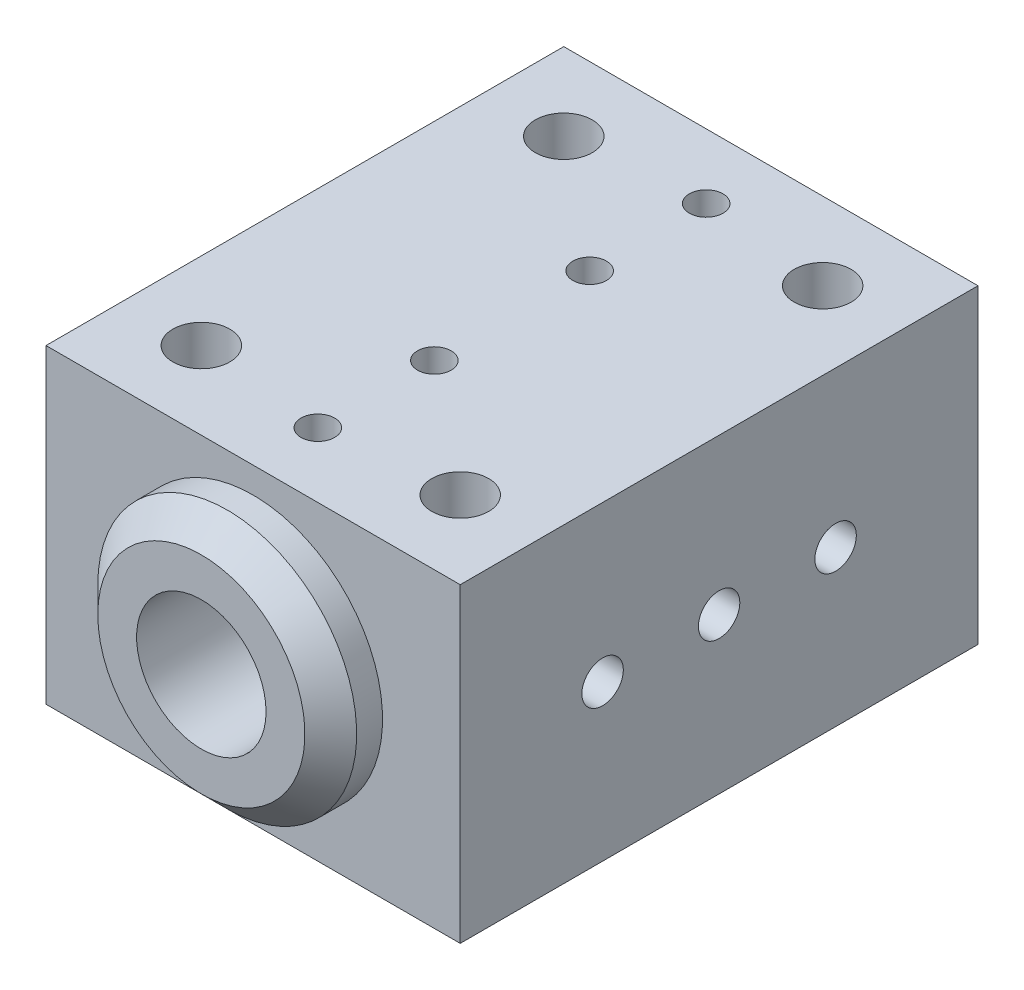
SolidWorks part; units mm, degrees
ref_plane "Front Plane" through (0, 0, 0) normal (0, 0, 1) x (1, 0, 0)
ref_plane "Top Plane" through (0, 0, 0) normal (0, 1, 0) x (1, 0, 0)
ref_plane "Right Plane" through (0, 0, 0) normal (1, 0, 0) x (0, 0, -1)
sketch "Base Sketch" plane through (0, 0, 0) normal (0, 1, 0) x (1, 0, 0)
  line L1 (-8, -10) -> (8, -10)
  line L2 (-8, -10) -> (-8, 10)
  line L3 (-8, 10) -> (8, 10)
  line L4 (8, -10) -> (8, 10)
  line L5 (-8, -10) -> (8, 10) construction
  line L6 (-8, 10) -> (8, -10) construction
  point P0 (0, 0)
  dimension "D1" = 20
  dimension "D2" = 16
extrude "Base Extrude" add sketch "Base Sketch" along normal blind 12
sketch "Protrusion Sketch" plane through (0, 0, 0) normal (0, 0, 1) x (1, 0, 0)
  line L0 (-8, 12) -> (-8, 0) construction
  circle A0 centre (0, 6) radius 5
  point P5 (-8, 6)
  dimension "D1" = 10
extrude "Top Protrusion Extrude" add sketch "Protrusion Sketch" along normal blind 2 from surface starting at face at (0, 6, 10)
extrude "Bottom Protrusion Extrude" add sketch "Protrusion Sketch<2>" against normal blind 2 from surface starting at face at (0, 6, -10)
sketch "Protrusion Sketch<2>" plane through (0, 0, 0) normal (0, 0, 1) x (1, 0, 0) same geometry as "Protrusion Sketch"
chamfer "Protrusion Chamfer" distance 1 2 edges at (5, 6, -12) (-5, 6, 12)
hole_wizard "Ø5.0mm Dowel Hole1" positions "Sketch3" profile "Sketch4" hole size "Ø5.0" standard "ANSI Metric" end condition through all
sketch "Sketch3" plane through (0, 0, 12) normal (0, 0, 1) x (1, 0, 0)
  point P0 (0, 6)
sketch "Sketch4" plane through (0, 6, 12) normal (1, 0, 0) x (0, -1, 0)
  line L0 (0, 0) -> (0, 24)
  line L1 (0, 24) -> (2.5, 24)
  line L2 (2.5, 24) -> (2.5, 0)
  line L5 (2.5, 0) -> (0, 0)
  line L11 (0, -6.35) -> (0, 107.95) construction
  dimension "Thru Hole Dia." = 5
  dimension "Thru Hole Depth" = 24
sketch "Right Hole Locations" plane through (0, 0, 0) normal (1, 0, 0) x (0, 0, -1)
  line L1 (-10, 12) -> (-10, 0) construction
  point P0 (0, 6)
  point P1 (4.5, 6)
  point P4 (-4.5, 6)
  point P5 (-10, 6)
  dimension "D1" = 4.5
  dimension "D2" = 4.5
hole_wizard "Ø1.6mm Dowel Hole1" positions "Sketch20" profile "Sketch21" hole size "Ø2.0" standard "ANSI Metric"
sketch "Sketch20" plane through (8, 0, 0) normal (1, 0, 0) x (0, 0, -1)
  point P0 (0, 6)
sketch "Sketch21" plane through (8, 6, 0) normal (0, 1, 0) x (0, 0, -1)
  line L0 (0, 0) -> (0, 8.4807)
  line L1 (0, 8.4807) -> (0.8, 8)
  line L2 (0.8, 8) -> (0.8, 0)
  line L5 (0.8, 0) -> (0, 0)
  line L10 (0, 8.4807) -> (-0.8, 8) construction
  line L11 (0, -6.35) -> (0, 107.95) construction
  dimension "Hole Dia." = 1.6
  dimension "Hole Depth" = 8
  dimension "Drill Angle" = 118
hole_wizard "Ø1.6 (1.6) Diameter Hole4" positions "Sketch39" profile "Sketch40" hole size "Ø1.6" standard "ANSI Metric"
sketch "Sketch39" plane through (-8, 0, 0) normal (-1, 0, 0) x (0, 0, 1)
  point P0 (0, 6)
sketch "Sketch40" plane through (-8, 6, 0) normal (0, 1, 0) x (0, 0, 1)
  line L0 (0, 0) -> (0, 3.9807)
  line L1 (0, 3.9807) -> (0.8, 3.5)
  line L2 (0.8, 3.5) -> (0.8, 0)
  line L5 (0.8, 0) -> (0, 0)
  line L10 (0, 3.9807) -> (-0.8, 3.5) construction
  line L11 (0, -6.35) -> (0, 107.95) construction
  dimension "Hole Dia." = 1.6
  dimension "Hole Depth" = 3.5
  dimension "Drill Angle" = 118
hole_wizard "M2x0.4 Tapped Hole1" positions "Sketch41" profile "Sketch42" tap size "M2x0.4" standard "ANSI Metric"
sketch "Sketch41" plane through (8, 0, 0) normal (1, 0, 0) x (0, 0, -1)
  point P0 (-4.5, 6)
  point P3 (4.5, 6)
sketch "Sketch42" plane through (8, 6, 4.5) normal (0, 1, 0) x (0, 0, -1)
  line L0 (0, 0) -> (0, 4.4807)
  line L1 (0, 4.4807) -> (0.8, 4)
  line L2 (0.8, 4) -> (0.8, 0)
  line L5 (0.8, 0) -> (0, 0)
  line L10 (0, 4.4807) -> (-0.8, 4) construction
  line L11 (0, -6.35) -> (0, 107.95) construction
  dimension "Tap Drill Dia." = 1.6
  dimension "Tap Drill Depth" = 4
  dimension "Drill Angle" = 118
cosmetic thread "Hole Thread1" parameters "D1"=4, "D2"=2
cosmetic thread "Hole Thread2" parameters "D1"=4, "D2"=2
hole_wizard "M2x0.4 Tapped Hole2" positions "Sketch43" profile "Sketch44" tap size "M2x0.4" standard "ANSI Metric"
sketch "Sketch43" plane through (-8, 0, 0) normal (-1, 0, 0) x (0, 0, 1)
  point P0 (-4.5, 6)
  point P3 (4.5, 6)
sketch "Sketch44" plane through (-8, 6, -4.5) normal (0, 1, 0) x (0, 0, 1)
  line L0 (0, 0) -> (0, 4.4807)
  line L1 (0, 4.4807) -> (0.8, 4)
  line L2 (0.8, 4) -> (0.8, 0)
  line L5 (0.8, 0) -> (0, 0)
  line L10 (0, 4.4807) -> (-0.8, 4) construction
  line L11 (0, -6.35) -> (0, 107.95) construction
  dimension "Tap Drill Dia." = 1.6
  dimension "Tap Drill Depth" = 4
  dimension "Drill Angle" = 118
cosmetic thread "Hole Thread3" parameters "D1"=4, "D2"=2
cosmetic thread "Hole Thread4" parameters "D1"=4, "D2"=2
sketch "Top Hole Locations" plane through (0, 0, 0) normal (0, 1, 0) x (1, 0, 0)
  line L0 (-8, 10) -> (-8, -10) construction
  line L1 (-5, -7) -> (5, -7) construction
  line L2 (-5, -7) -> (-5, 7) construction
  line L3 (-5, 7) -> (5, 7) construction
  line L4 (5, -7) -> (5, 7) construction
  line L5 (-5, -7) -> (5, 7) construction
  line L6 (-5, 7) -> (5, -7) construction
  line L7 (8, 10) -> (-8, 10) construction
  point P0 (0, 0)
  dimension "D1" = 3
  dimension "D2" = 3
hole_wizard "Ø2.2 (2.2) Diameter Hole1" positions "Sketch16" profile "Sketch17" hole size "Ø2.2" standard "ANSI Metric" end condition through all
sketch "Sketch16" plane through (0, 12, 0) normal (0, 1, 0) x (1, 0, 0)
  point P0 (-5, 7)
  point P3 (5, 7)
  point P6 (-5, -7)
  point P9 (5, -7)
sketch "Sketch17" plane through (-5, 12, -7) normal (1, 0, 0) x (0, 0, 1)
  line L0 (0, 0) -> (0, 12)
  line L1 (0, 12) -> (1.1, 12)
  line L2 (1.1, 12) -> (1.1, 0)
  line L5 (1.1, 0) -> (0, 0)
  line L11 (0, -6.35) -> (0, 107.95) construction
  dimension "Thru Hole Dia." = 2.2
  dimension "Thru Hole Depth" = 12
sketch "Hole Locations For Slots" plane through (0, 0, 0) normal (0, 1, 0) x (1, 0, 0)
  line L0 (-8, 10) -> (-8, -10) construction
  line L4 (-4, -12) -> (4, -12) construction
  line L5 (4, 12) -> (-4, 12) construction
  point P0 (0, 7.5)
  point P1 (0, 3)
  point P2 (0, -3)
  point P3 (0, -7.5)
  point P9 (-5, 0)
  dimension "D1" = 4.5
  dimension "D2" = 4.5
  dimension "D3" = 4.5
  dimension "D4" = 4.5
  dimension "D5" = 3
hole_wizard "Ø1.3 (1.3) Diameter Hole1" positions "Sketch31" profile "Sketch32" hole size "Ø1.3" standard "ANSI Metric"
sketch "Sketch31" plane through (0, 0, 0) normal (0, -1, 0) x (-1, 0, 0)
  point P0 (0, 7.5)
  point P3 (0, -7.5)
sketch "Sketch32" plane through (0, 0, -7.5) normal (1, 0, 0) x (0, 0, -1)
  line L0 (0, 0) -> (0, 6.3906)
  line L1 (0, 6.3906) -> (0.65, 6)
  line L2 (0.65, 6) -> (0.65, 0)
  line L5 (0.65, 0) -> (0, 0)
  line L10 (0, 6.3906) -> (-0.65, 6) construction
  line L11 (0, -6.35) -> (0, 107.95) construction
  dimension "Hole Dia." = 1.3
  dimension "Hole Depth" = 6
  dimension "Drill Angle" = 118
hole_wizard "Ø1.3 (1.3) Diameter Hole2" positions "Sketch35" profile "Sketch36" hole size "Ø1.3" standard "ANSI Metric"
sketch "Sketch35" plane through (0, 0, 0) normal (0, -1, 0) x (-1, 0, 0)
  point P0 (5, 0)
sketch "Sketch36" plane through (-5, 0, 0) normal (1, 0, 0) x (0, 0, -1)
  line L0 (0, 0) -> (0, 6.3906)
  line L1 (0, 6.3906) -> (0.65, 6)
  line L2 (0.65, 6) -> (0.65, 0)
  line L5 (0.65, 0) -> (0, 0)
  line L10 (0, 6.3906) -> (-0.65, 6) construction
  line L11 (0, -6.35) -> (0, 107.95) construction
  dimension "Hole Dia." = 1.3
  dimension "Hole Depth" = 6
  dimension "Drill Angle" = 118
hole_wizard "Ø1.3 (1.3) Diameter Hole3" positions "Sketch37" profile "Sketch38" hole size "Ø1.3" standard "ANSI Metric"
sketch "Sketch37" plane through (0, 12, 0) normal (0, 1, 0) x (1, 0, 0)
  point P0 (0, -7.5)
  point P3 (0, -3)
  point P6 (0, 3)
  point P9 (0, 7.5)
sketch "Sketch38" plane through (0, 12, 7.5) normal (1, 0, 0) x (0, 0, 1)
  line L0 (0, 0) -> (0, 6.3906)
  line L1 (0, 6.3906) -> (0.65, 6)
  line L2 (0.65, 6) -> (0.65, 0)
  line L5 (0.65, 0) -> (0, 0)
  line L10 (0, 6.3906) -> (-0.65, 6) construction
  line L11 (0, -6.35) -> (0, 107.95) construction
  dimension "Hole Dia." = 1.3
  dimension "Hole Depth" = 6
  dimension "Drill Angle" = 118
